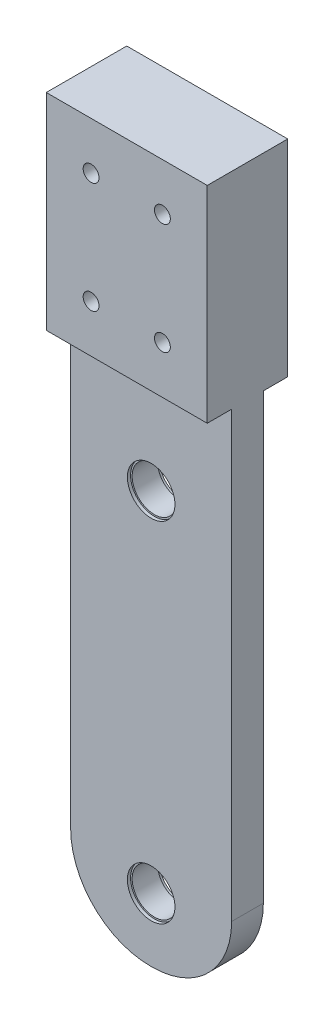
SolidWorks part; units mm, degrees
ref_plane "Front Plane" through (0, 0, 0) normal (0, 0, 1) x (1, 0, 0)
ref_plane "Top Plane" through (0, 0, 0) normal (0, 1, 0) x (1, 0, 0)
ref_plane "Right Plane" through (0, 0, 0) normal (1, 0, 0) x (0, 0, -1)
sketch "Sketch1" plane through (0, 0, 0) normal (0, 0, 1) x (1, 0, 0)
  line L0 (-25.4, 0) -> (-25.4, 100)
  line L1 (-25.4, 100) -> (25.4, 100)
  line L2 (25.4, 100) -> (25.4, 0)
  line L3 (-25.4, 0) -> (-25.4, -105)
  line L4 (-11.25, 85) -> (11.25, 85) construction
  line L5 (-11.25, 85) -> (-11.25, 50) construction
  line L6 (-11.25, 50) -> (11.25, 50) construction
  line L7 (11.25, 85) -> (11.25, 50) construction
  line L8 (0, 0) -> (0, -110) construction
  line L9 (-0.4, -130) -> (0.4, -130)
  line L10 (25.4, 0) -> (25.4, -105)
  circle A0 centre (0, 0) radius 7
  circle A2 centre (-11.25, 85) radius 2.5
  circle A3 centre (11.25, 85) radius 2.5
  circle A4 centre (11.25, 50) radius 2.5
  circle A5 centre (-11.25, 50) radius 2.5
  circle A6 centre (0, -110) radius 7
  arc A7 (25.4, -105) -> (0.4, -130) centre (0.4, -105) cw
  arc A8 (-25.4, -105) -> (-0.4, -130) centre (-0.4, -105) ccw
  point P13 (0, 50)
  point P25 (0, 100)
  dimension "D1" = 14
  dimension "D4" = 5
  dimension "D9" = 14
  dimension "D11" = 25
  dimension "D2" = 50.8
  dimension "D3" = 100
  dimension "D5" = 35
  dimension "D6" = 15
  dimension "D7" = 22.5
  dimension "D8" = 110
  dimension "D10" = 20
extrude "Boss-Extrude1" add sketch "Sketch1" along normal mid plane 10 from surface starting at plane "Front Plane"
sketch "Sketch3" plane through (0, 0, 0) normal (0, 0, 1) x (1, 0, 0)
  line L0 (25.4, 100) -> (25.4, -105) construction
  line L1 (-25.4, 100) -> (25.4, 100)
  line L2 (-25.4, 100) -> (-25.4, 35)
  line L3 (-25.4, 35) -> (25.4, 35)
  line L4 (25.4, 100) -> (25.4, 35)
  line L5 (-11.25, 85) -> (-11.25, 100) construction
  line L6 (-11.25, 50) -> (-11.25, 35) construction
  circle A0 centre (-11.25, 50) radius 2.5
  circle A1 centre (11.25, 50) radius 2.5
  circle A2 centre (11.25, 85) radius 2.5
  circle A3 centre (-11.25, 85) radius 2.5
  circle A4 centre (-11.25, 85) radius 2.5 construction
extrude "Boss-Extrude2" add sketch "Sketch3" along normal mid plane 25.4
sketch "Sketch4" plane through (0, 0, 5) normal (0, 0, 1) x (1, 0, 0)
  circle A0 centre (0, -110) radius 7.5
  dimension "D1" = 15
extrude "Cut-Extrude1" cut sketch "Sketch4" against normal blind 1
sketch "Sketch5" plane through (0, 0, -5) normal (0, 0, -1) x (-1, 0, 0)
  circle A0 centre (0, -110) radius 7.5
  dimension "D1" = 15
extrude "Cut-Extrude2" cut sketch "Sketch5" against normal blind 1
sketch "Sketch6" plane through (0, 0, 5) normal (0, 0, 1) x (1, 0, 0)
  circle A0 centre (0, 0) radius 7.5
  dimension "D1" = 15
extrude "Cut-Extrude3" cut sketch "Sketch6" against normal blind 1
sketch "Sketch7" plane through (0, 0, -5) normal (0, 0, -1) x (-1, 0, 0)
  circle A0 centre (0, 0) radius 7.5
  dimension "D1" = 15
extrude "Cut-Extrude4" cut sketch "Sketch7" against normal blind 1
equation "\"tube_length\"= 1.5ft"
